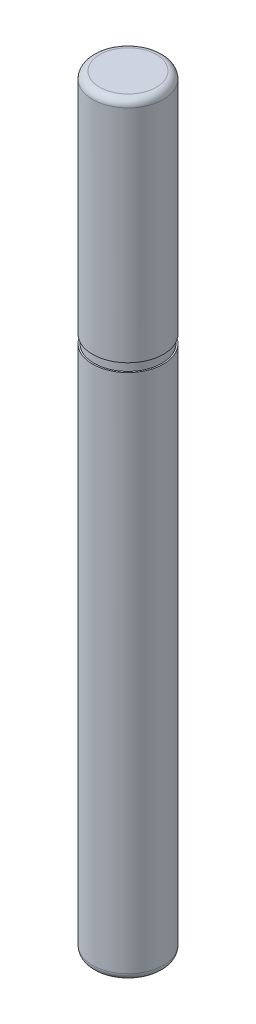
SolidWorks part; units mm, degrees
material "Plain Carbon Steel"
ref_plane "Front Plane" through (0, 0, 0) normal (0, 0, 1) x (1, 0, 0)
ref_plane "Top Plane" through (0, 0, 0) normal (0, 1, 0) x (1, 0, 0)
ref_plane "Right Plane" through (0, 0, 0) normal (1, 0, 0) x (0, 0, -1)
sketch "Sketch1" plane through (0, 0, 0) normal (0, -1, 0) x (1, 0, 0)
  circle A0 centre (0, 0) radius 2.5
  dimension "D1" = 5
extrude "Boss-Extrude1" add sketch "Sketch1" along normal mid plane 54
sketch "Sketch4" plane through (0, 27, 0) normal (0, 1, 0) x (1, 0, 0)
  line L0 (-1.5, 2) -> (1.5, 2)
  arc A0 (1.5, 2) -> (-1.5, 2) centre (0, 0) ccw
  dimension "D1" = 5
  dimension "D2" = 0.5
extrude "Cut-Extrude2" cut sketch "Sketch4" against normal blind 2.5 from offset 7 offset against normal yes
extrude "Cut-Extrude3" cut sketch "Sketch4<2>" against normal blind 6 from offset 46.5 offset against normal yes
sketch "Sketch4<2>" plane through (0, 27, 0) normal (0, 1, 0) x (1, 0, 0) same geometry as "Sketch4"
fillet "Fillet1" radius 0.5 2 edges at (0, -27, -2.5) (0, 27, -2.5)
sketch "Sketch5" plane through (0, 0, 0) normal (0, 0, 1) x (1, 0, 0)
  line L0 (2, 27) -> (-2, 27) construction
  line L1 (2.4, 10.9) -> (4.4, 10.9)
  line L2 (2.4, 10.9) -> (2.4, 10.3)
  line L3 (2.4, 10.3) -> (4.4, 10.3)
  line L4 (4.4, 10.9) -> (4.4, 10.3)
  line L5 (0, 0) -> (0, 27) construction
  dimension "D1" = 0.6
  dimension "D2" = 16.1
  dimension "D3" = 4.8
  dimension "D4" = 2
revolve "Cut-Revolve2" cut sketch "Sketch5" angle 360 about L5
